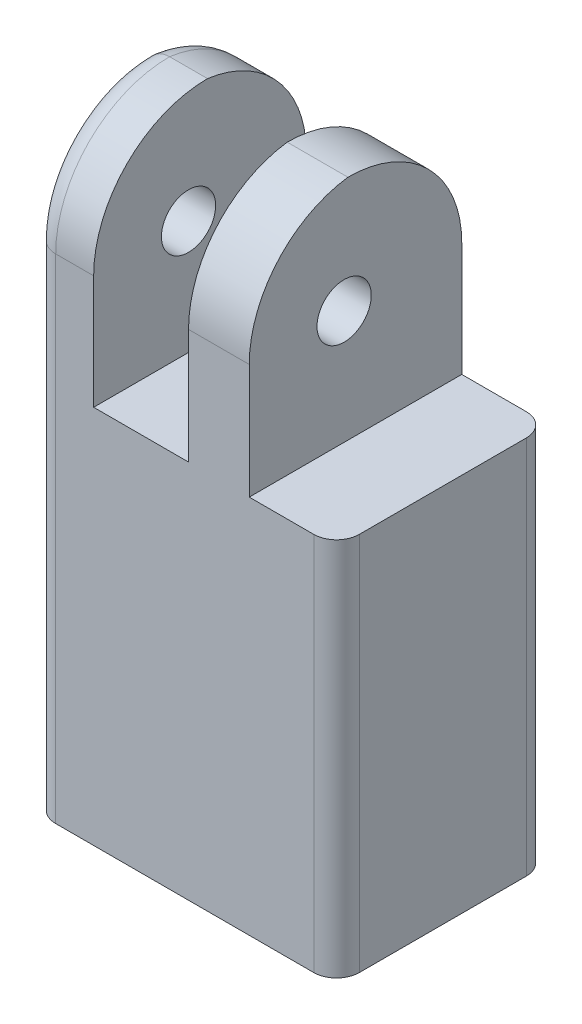
SolidWorks part; units mm, degrees
ref_plane "Front Plane" through (0, 0, 0) normal (0, 0, 1) x (1, 0, 0)
ref_plane "Top Plane" through (0, 0, 0) normal (0, 1, 0) x (1, 0, 0)
ref_plane "Right Plane" through (0, 0, 0) normal (1, 0, 0) x (0, 0, -1)
sketch "Sketch2" plane through (0, 0, 0) normal (0, 1, 0) x (1, 0, 0)
  line L1 (0, 0) -> (40, 0)
  line L2 (0, 0) -> (0, 28)
  line L3 (0, 28) -> (40, 28)
  line L4 (40, 0) -> (40, 28)
  dimension "D1" = 40
  dimension "D2" = 28
extrude "Boss-Extrude2" add sketch "Sketch2" along normal blind 50
sketch "Sketch3" plane through (0, 50, 0) normal (0, 1, 0) x (1, 0, 0)
  line L0 (0, 0) -> (40, 0) construction
  line L1 (0, 28) -> (8, 28)
  line L2 (0, 28) -> (0, 0)
  line L3 (0, 0) -> (8, 0)
  line L4 (8, 28) -> (8, 0)
  line L5 (40, 28) -> (0, 28) construction
  line L6 (20.5, 28) -> (28.5, 28)
  line L7 (20.5, 28) -> (20.5, 0)
  line L8 (20.5, 0) -> (28.5, 0)
  line L9 (28.5, 28) -> (28.5, 0)
  dimension "D1" = 8
  dimension "D2" = 12.5
  dimension "D3" = 8
extrude "Boss-Extrude3" add sketch "Sketch3" along normal blind 30
hole_wizard "9/32 (0.28125) Diameter Hole1" positions "3DSketch1" profile "Sketch4" hole size "9/32" standard "ANSI Inch" end condition through all
sketch3d "3DSketch1"
  line L0 (0, 80, 0) -> (0, 0, 0) construction
  line L2 (0, 80, -28) -> (0, 80, 0) construction
  point P0 (0, 65, -12.5)
  dimension "D1" = 12.5
  dimension "D2" = 15
sketch "Sketch4" plane through (0, 65, -12.5) normal (0, 1, 0) x (0, 0, 1)
  line L0 (0, 0) -> (0, 40)
  line L1 (0, 40) -> (3.5719, 40)
  line L2 (3.5719, 40) -> (3.5719, 0.635)
  line L3 (3.5719, 0.635) -> (4.2069, 0)
  line L5 (4.2069, 0) -> (0, 0)
  line L6 (-3.5719, 0.635) -> (-4.2069, 0) construction
  line L11 (0, -6.35) -> (0, 107.95) construction
  dimension "Thru Hole Dia." = 7.1437
  dimension "Thru Hole Depth" = 40
  dimension "Near C'Sink Dia." = 8.4137
  dimension "Near C'Sink Angle" = 90
fillet "Fillet5" radius 15 1 edges at (4, 80, 0)
fillet "Fillet3" radius 15 1 edges at (24.5, 80, -28)
fillet "Fillet4" radius 15 1 edges at (24.5, 80, 0)
fillet "Fillet6" radius 15 1 edges at (4, 80, -28)
fillet "Fillet7" radius 3 4 edges at (0, 75.6066, -4.3934) (0, 75.0081, -24.2916) (0, 32.5, 0) (0, 32.567, -28)
fillet "Fillet8" radius 3 2 edges at (40, 25, -28) (40, 25, 0)
